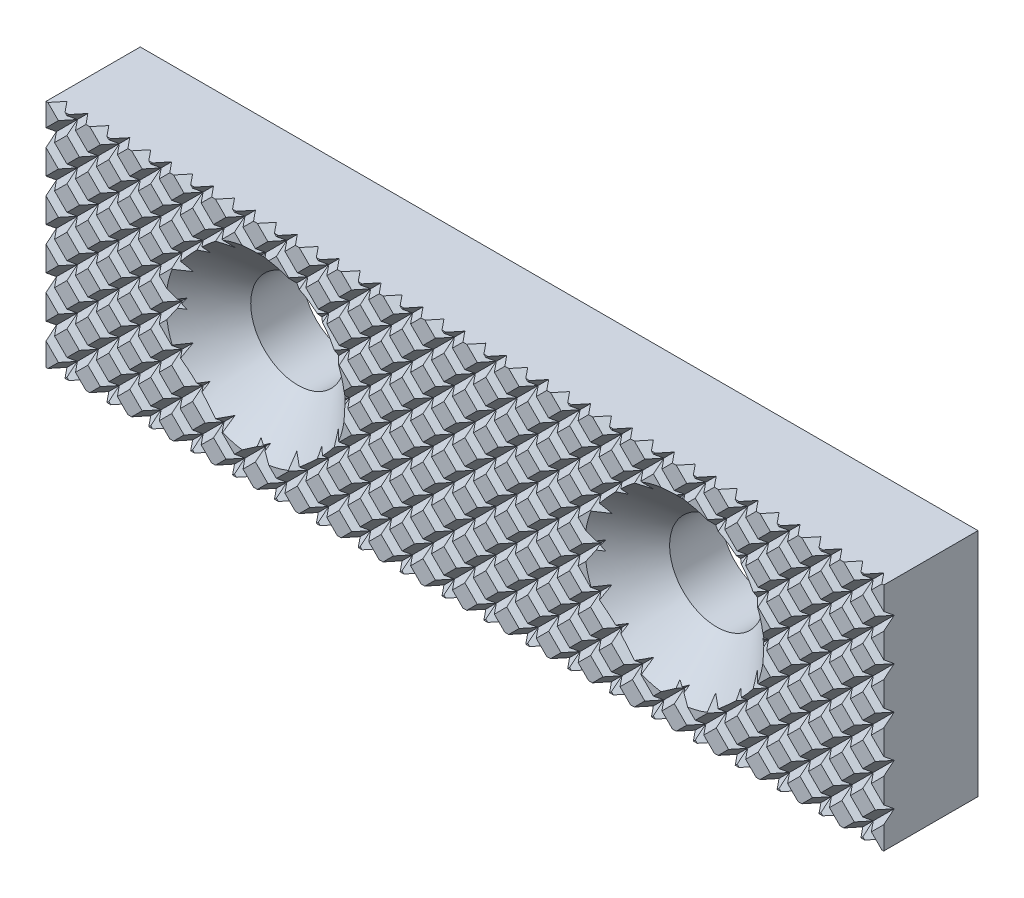
SolidWorks part; units mm, degrees
material "40Cr"
ref_plane "前视基准面" through (0, 0, 0) normal (0, 0, 1) x (1, 0, 0)
ref_plane "上视基准面" through (0, 0, 0) normal (0, 1, 0) x (1, 0, 0)
ref_plane "右视基准面" through (0, 0, 0) normal (1, 0, 0) x (0, 0, -1)
sketch "草图1" plane through (0, 0, 0) normal (0, 0, 1) x (1, 0, 0)
  line L0 (-40, -11) -> (40, -11)
  line L1 (-40, -11) -> (-40, 11)
  line L2 (40, -11) -> (40, 11)
  line L3 (-40, 11) -> (40, 11)
  line L4 (0, -20.2694) -> (0, 30.2153) construction
  line L5 (-44.0064, 0) -> (47.7622, 0) construction
  dimension "D1" = 22
  dimension "D2" = 80
extrude "凸台-拉伸3" add sketch "草图1" along normal blind 9
sketch "草图6" plane through (0, 0, 9) normal (0, 0, 1) x (1, 0, 0)
  line L0 (-44.0064, 0) -> (47.7622, 0) construction
  line L1 (0, -20.2694) -> (0, 30.2153) construction
  line L2 (0, -20.2694) -> (0, 30.2153) construction
  line L3 (-44.0064, 0) -> (47.7622, 0) construction
  circle A0 centre (-20, 0) radius 4.5
  circle A1 centre (20, 0) radius 4.5
  dimension "D1" = 9
  dimension "D2" = 40
extrude "切除-拉伸2" cut sketch "草图6" against normal through all
chamfer "倒角1" distance 4.05 angle 45 1 edges at (-15.5, 0, 9)
chamfer "倒角2" distance 4.05 angle 45 1 edges at (15.5, 0, 9)
ref_axis "基准轴2" through (-40, 0, 9) along (0, 0, -1)
ref_plane "基准面1" through (-20, -20, 0) normal (-0.7071, -0.7071, 0) x (0.7071, -0.7071, 0)
sketch "草图7" plane through (-20, -20, 0) normal (-0.7071, -0.7071, 0) x (0.7071, -0.7071, 0)
  line L0 (0, -2.1356) -> (0, 14.0426) construction
  line L1 (0, 8) -> (-0.5774, 9)
  line L2 (-20.5061, 9) -> (36.0624, 9) construction
  line L3 (0, 8) -> (0.5774, 9)
  line L4 (0.5774, 9) -> (-0.5774, 9)
  dimension "D1" = 60
  dimension "D2" = 1
extrude "切除-拉伸3" cut sketch "草图7" against normal through all
pattern_linear "阵列(线性)4" count 13 spacing 4 along (-1, 0, 0) of "切除-拉伸3"
pattern_linear "阵列(线性)5" count 15 spacing 4 along (1, 0, 0) of "切除-拉伸3"
mirror "镜向1" about plane through (0, 0, 0) normal (1, 0, 0) of "阵列(线性)4", "阵列(线性)5"
